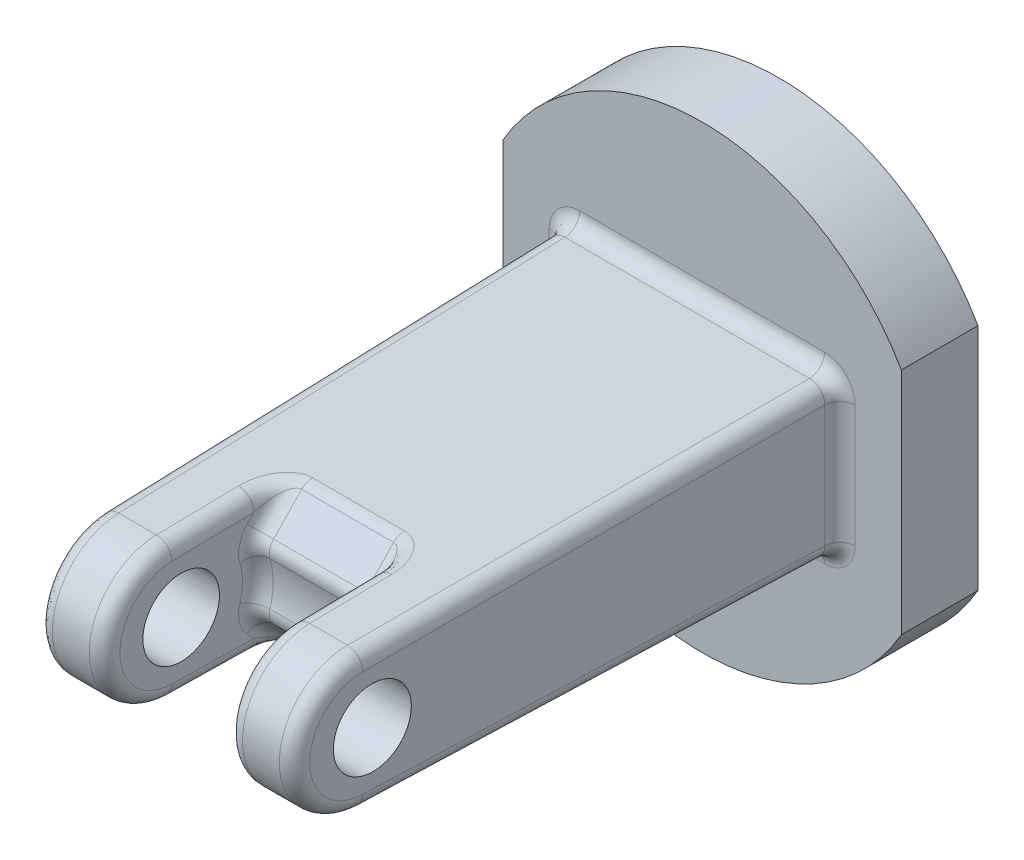
SolidWorks part; units mm, degrees
ref_plane "前视基准面" through (0, 0, 0) normal (0, 0, 1) x (1, 0, 0)
ref_plane "上视基准面" through (0, 0, 0) normal (0, 1, 0) x (1, 0, 0)
ref_plane "右视基准面" through (0, 0, 0) normal (1, 0, 0) x (0, 0, -1)
ref_plane "基准面4" through (-90, 0, 0) normal (-1, 0, 0) x (0, -1, 0)
sketch "草图1" plane through (-90, 0, 0) normal (-1, 0, 0) x (0, -1, 0)
  line L0 (-44.6567, 356.116) -> (-50, 50)
  line L1 (-50, 50) -> (50, 50)
  line L2 (50, 50) -> (44.6567, 356.116)
  arc A0 (44.6567, 356.116) -> (-44.6567, 356.116) centre (0, 355.3365) ccw
extrude "凸台-拉伸1" add sketch "草图1" against normal blind 180
ref_plane "基准面5" through (-40, 0, 0) normal (-1, 0, 0) x (0, -1, 0)
sketch "草图2" plane through (-40, 0, 0) normal (-1, 0, 0) x (0, -1, 0)
  line L0 (-44.6567, 356.116) -> (-46.0115, 278.5022)
  line L1 (-46.0115, 278.5022) -> (-19.6041, 304.0035)
  line L2 (19.6041, 304.0035) -> (46.0115, 278.5022)
  line L3 (46.0115, 278.5022) -> (44.6567, 356.116)
  arc A0 (-19.6041, 304.0035) -> (19.6041, 304.0035) centre (0, 350) ccw
  arc A1 (44.6567, 356.116) -> (-44.6567, 356.116) centre (0, 355.3365) ccw
extrude "切除-拉伸1" cut sketch "草图2" against normal blind 80
ref_plane "基准面6" through (0, 0, 50) normal (0, 0, 1) x (1, 0, 0)
sketch "草图3" plane through (0, 0, 50) normal (0, 0, 1) x (1, 0, 0)
  line L0 (130, -74.8331) -> (130, 74.8331)
  line L1 (-130, 74.8331) -> (-130, -74.8331)
  arc A0 (130, 74.8331) -> (-130, 74.8331) centre (0, 0) ccw
  arc A1 (-130, -74.8331) -> (130, -74.8331) centre (0, 0) ccw
extrude "凸台-拉伸2" add sketch "草图3" against normal blind 50
draft "拔模1" type of draft neutral plane draft angle 1 faces to draft 2 face at (90, 0, 214.029) face at (-90, 0, 214.029) neutral plane through (0, 0, 50) neutral plane normal (0, 0, 1) parameters "D1"=1
sketch "草图4" plane through (0, 0, 0) normal (0, 1, 0) x (1, 0, 0)
  line L0 (50, 50) -> (0, 50)
  line L1 (0, 50) -> (0, 0)
  line L2 (0, 0) -> (50, 0)
  line L3 (50, 0) -> (50, 50)
  line L4 (0, 50) -> (0, 0) construction
revolve "旋转1" add sketch "草图4" angle 360 about L4 reverse direction yes
hole_wizard "孔1" positions "草图6" profile "草图5" legacy
sketch "草图6" plane through (40, 0, 0) normal (-1, 0, 0) x (0, 0, 1)
  point P0 (350, 0)
sketch "草图5" plane through (40, 0, 350) normal (0, 1, 0) x (0, 0, 1)
  line L0 (0, 0) -> (0, 90)
  line L1 (0, 90) -> (25, 90)
  line L2 (25, 90) -> (25, 0)
  line L3 (25, 0) -> (0, 0)
  line L4 (0, 110) -> (0, -10) construction
  dimension "直径" = 50
  dimension "深度" = 90
hole_wizard "孔2" positions "草图8" profile "草图7" legacy
sketch "草图8" plane through (-40, 0, 0) normal (1, 0, 0) x (0, 0, -1)
  point P0 (-350, 0)
sketch "草图7" plane through (-40, 0, 350) normal (0, 1, 0) x (0, 0, -1)
  line L0 (0, 0) -> (0, 90)
  line L1 (0, 90) -> (25, 90)
  line L2 (25, 90) -> (25, 0)
  line L3 (25, 0) -> (0, 0)
  line L4 (0, 110) -> (0, -10) construction
  dimension "直径" = 50
  dimension "深度" = 90
fillet "圆角1" radius 10 26 edges at (0, -50, 50) (90, 0, 50) (0, 50, 50) (-90, 0, 50) (0, -46.0115, 278.5022) (40, -32.8078, 291.2528) (-40, -45.3341, 317.3091) (40, -45.3341, 317.3091) (-40, 0, 400) (40, 0, 400) (-40, 45.3341, 317.3091) (40, 45.3341, 317.3091) (-40, 32.8078, 291.2528) (0, 46.0115, 278.5022) (-87.3284, -47.3284, 203.058) (-87.3284, 47.3284, 203.058) (-83.8907, 0, 400) (87.3284, 47.3284, 203.058) (83.8907, 0, 400) (87.3284, -47.3284, 203.058) (-40, -32.8078, 291.2528) (-40, 0, 300) (40, 32.8078, 291.2528) (0, 19.6041, 304.0035) (40, 0, 300) (0, -19.6041, 304.0035) tangent propagation no
